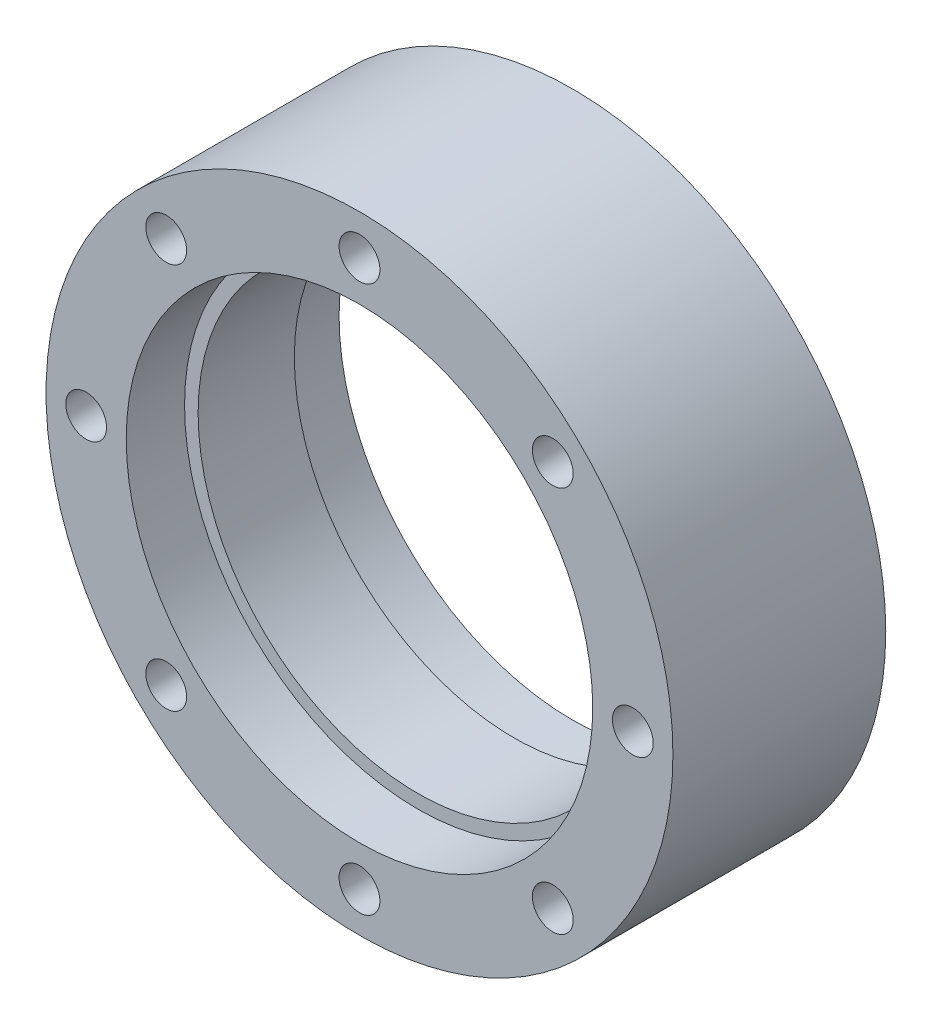
SolidWorks part; units mm, degrees
ref_plane "Front Plane" through (0, 0, 0) normal (0, 0, 1) x (1, 0, 0)
ref_plane "Top Plane" through (0, 0, 0) normal (0, 1, 0) x (1, 0, 0)
ref_plane "Right Plane" through (0, 0, 0) normal (1, 0, 0) x (0, 0, -1)
ref_axis "Z" through (0, 0, 8.03) along (0, 0, -1)
sketch "Sketch7" plane through (0, 0, 0) normal (0, 1, 0) x (1, 0, 0)
  line L0 (16, 7.3) -> (16, 3.3)
  line L2 (16, 3.3) -> (15.07, 3.3)
  line L5 (16, 7.3) -> (21.5, 7.3)
  line L6 (21.5, 7.3) -> (21.5, -7.3)
  line L7 (24.7452, 0) -> (-6.4078, 0) construction
  line L8 (16, -3.3) -> (15.07, -3.3)
  line L9 (16, -7.3) -> (16, -3.3)
  line L10 (15.07, 3.3) -> (15.07, -3.3)
  line L11 (21.5, -7.3) -> (16, -7.3)
  line L12 (0, -8.03) -> (0, 8.03) construction
  dimension "D2" = 4
  dimension "D4" = 3.3
  dimension "D1" = 15.07
  dimension "D3" = 16
  dimension "D5" = 21.5
revolve "Revolve1" add sketch "Sketch7" angle 360 about axis through (0, 0, 8.03) along (0, 0, -1)
sketch "Sketch3" plane through (0, 0, 0) normal (0, 0, 1) x (1, 0, 0)
  line L0 (0, 0) -> (0, 18.75) construction
  circle A0 centre (0, 18.75) radius 1.4
  dimension "D1" = 2.8
  dimension "D2" = 18.75
extrude "Cut-Extrude2" cut sketch "Sketch3" against normal through all both and the other way through all
sketch "Sketch4" plane through (0, 0, -7.3) normal (0, 0, -1) x (-1, 0, 0)
  circle A0 centre (0, 18.75) radius 2.35
  circle A1 centre (0, 18.75) radius 1.4 construction
  dimension "D1" = 4.7
extrude "Cut-Extrude4" cut sketch "Sketch4" against normal blind 2.5 and the other way through all
chamfer "Chamfer1" distance 0.1 angle 45 1 edges at (-1.4, 18.75, -4.8)
pattern_circular "CirPattern3" count 4 over 360 about axis through (0, 0, 8.03) along (0, 0, -1) of "Cut-Extrude4"
pattern_circular "CirPattern2" count 8 over 360 about axis through (0, 0, 8.03) along (0, 0, -1) of "Cut-Extrude2"
equation "\"BearingOD\"= 32"
equation "\"BearingHeight\"= 4"
equation "\"SeatsOD\"= \"BearingOD\" + 10"
equation "\"RetainingRingThickness\" = 1.30"
equation "\"BearingBaseDistance\"= 17.2 - 2*\"BearingHeight\"  - \"RetainingRingThickness\"*2"
equation "\"WireHarnessHeight\"= 4"
equation "\"OuterWallWidth\"= 6"
equation "\"OverallOD\" = 43"
equation "\"BearingID\" = 25"
equation "\"OverallHeight\"= \"WireHarnessHeight\" + \"BearingHeight\"*2 + \"BearingBaseDistance\""
equation "\"RetaininRingGrooveDiameter\" = 23.9"
equation "\"ShaftLengthAfterFlange\" = 2*\"BearingHeight\" + \"BearingBaseDistance\" + \"RetainingRingThickness\"*2\t'give a retaining ring thickness of extra clearance"
equation "\"RetainingRingGrooveBase\" = \"ShaftLengthAfterFlange\" - \"RetainingRingThickness\"*2"
equation "\"CoverThickness\" = 1"
equation "\"CoverClearance\" = 1"
equation "\"FlangHeight\" = 3"
equation "\"OuterHousingHeight\" = \"WireHarnessHeight\" + \"BearingHeight\"*2 + \"BearingBaseDistance\""
equation "\"PCBWidth\" = 5"
equation "\"PCBHeight\" = \"OuterHousingHeight\" "
equation "\"PCBThickness\" = 1"
equation "\"NormalDistSidewallPCBToZ\" = (\"OverallOD\"/2) - 1.6\t'radial distance from the z axis to pcb origin on the top/connector side"
equation "\"PCBSidewallCutoutClearance\"= 0.1"
equation "\"D3@Sketch7\"=\"BearingOD\"/2"
equation "\"D4@Sketch7\"=\"BearingBaseDistance\"/2"
equation "\"D5@Sketch7\"=\"OverallOD\"/2"
equation "\"D2@Sketch3\"=(\"OverallOD\"+\"BearingOD\")/4"
equation "\"OutputHubBoltCircleRadius\"= 8"
equation "\"OutputHubOD\"= 27"
equation "\"BearingInnerRaceOD\"= 26.9"
equation "\"StatorWireRadius\"= \"NormalDistSidewallPCBToZ\" - 5.7"
equation "\"MountingHoleRadius\"= (\"OverallOD\"+\"BearingOD\")/4"
